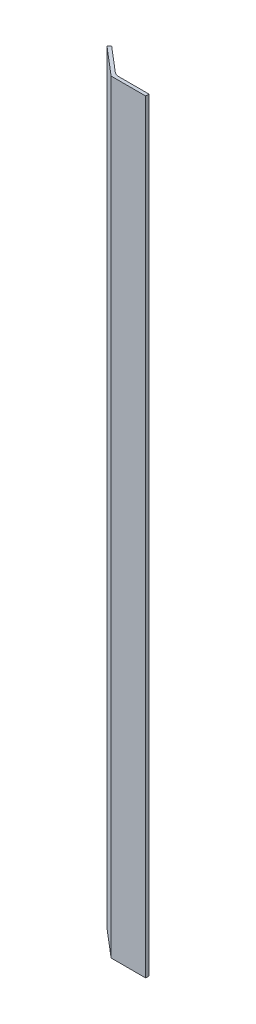
SolidWorks part; units mm, degrees
ref_plane "Спереди" through (0, 0, 0) normal (0, 0, 1) x (1, 0, 0)
ref_plane "Сверху" through (0, 0, 0) normal (0, 1, 0) x (1, 0, 0)
ref_plane "Справа" through (0, 0, 0) normal (1, 0, 0) x (0, 0, -1)
sketch "Эскиз1" plane through (0, 0, 0) normal (0, 1, 0) x (1, 0, 0)
  line L0 (-20.5084, 12.7927) -> (-19.212, 14.3155)
  line L1 (-1.1334, 0.4869) -> (17.1228, 0.4869)
  line L2 (-19.212, 14.3155) -> (-4.3752, 1.6802)
  line L3 (-20.5084, 12.7927) -> (-3.7046, -1.5131)
  line L4 (-3.7046, -1.5131) -> (17.1228, -1.5131)
  line L5 (17.1228, -1.5131) -> (17.1228, 0.4869)
  arc A0 (-1.1334, 0.4869) -> (-4.3752, 1.6802) centre (-1.1334, 5.4869) cw
  dimension "D1" = 5
extrude "Вытянуть1" add sketch "Эскиз1" along normal blind 460 from offset 40
sketch "Эскиз2" plane through (-2.3036, 0, 2.7059) normal (-0.6482, 0, 0.7614) x (0.7614, 0, 0.6482)
  line L0 (-29.2499, 538.7137) -> (-29.2499, 0) construction
  line L1 (-29.2499, 404.5977) -> (-14.4324, 404.5977)
  line L2 (-29.2499, 404.5977) -> (-29.2499, 229.6358)
  line L3 (-29.2499, 229.6358) -> (-14.4324, 229.6358)
  line L4 (-14.4324, 404.5977) -> (-14.4324, 229.6358)
extrude "Вырез-Вытянуть1" [suppressed] cut sketch "Эскиз2" against normal through all
